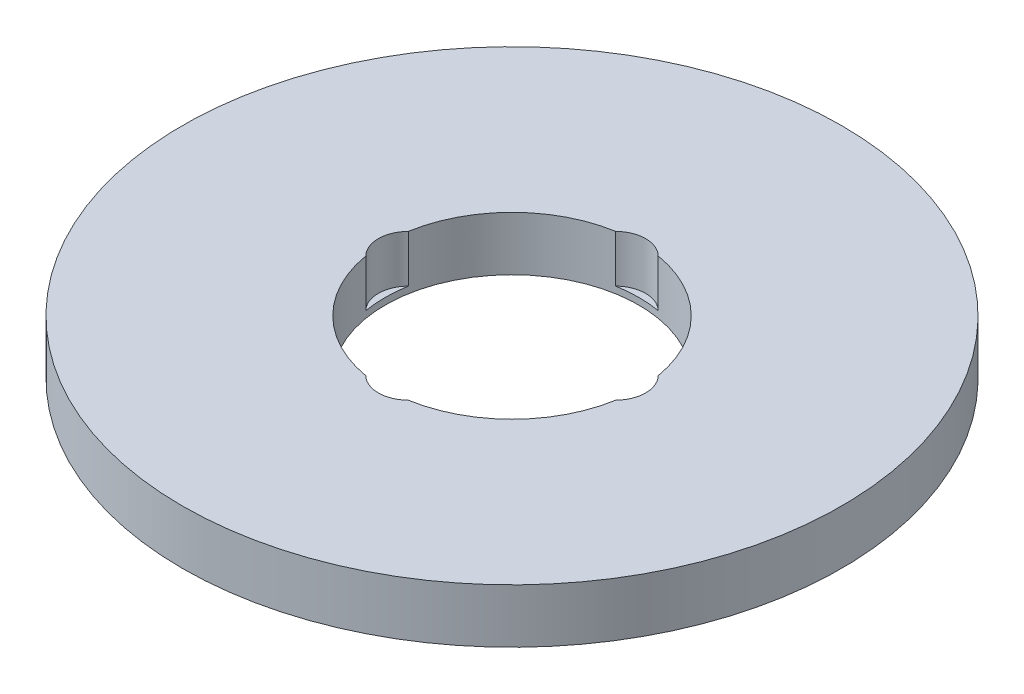
SolidWorks part; units mm, degrees
ref_plane "Front Plane" through (0, 0, 0) normal (0, 0, 1) x (1, 0, 0)
ref_plane "Top Plane" through (0, 0, 0) normal (0, 1, 0) x (1, 0, 0)
ref_plane "Right Plane" through (0, 0, 0) normal (1, 0, 0) x (0, 0, -1)
sketch "Sketch1" plane through (0, 0, 0) normal (0, 1, 0) x (1, 0, 0)
  circle A0 centre (0, 0) radius 97.5
  dimension "FLANGE_OD" = 195
extrude "Boss-Extrude1" add sketch "Sketch1" along normal blind 16
sketch "Sketch2" plane through (0, 0, 0) normal (0, 1, 0) x (1, 0, 0)
  circle A0 centre (0, 0) radius 37.5
  dimension "BORE_D" = 75
extrude "Cut-Extrude1" cut sketch "Sketch2" along normal through all
sketch "Sketch3" plane through (0, 16, 0) normal (0, 1, 0) x (1, 0, 0)
  circle A0 centre (0, 0) radius 30.5425 construction
  circle A1 centre (-30.5425, 0) radius 8.997
  dimension "BOLT_D" = 17.9939
  dimension "BOLT_PCD" = 61.0849
extrude "Cut-Extrude2" cut sketch "Sketch3" against normal blind 14.0282
pattern_circular "CirPattern1" count 4 over 360 about axis through (0, 0, 0) along (0, 1, 0) of "Cut-Extrude2"
